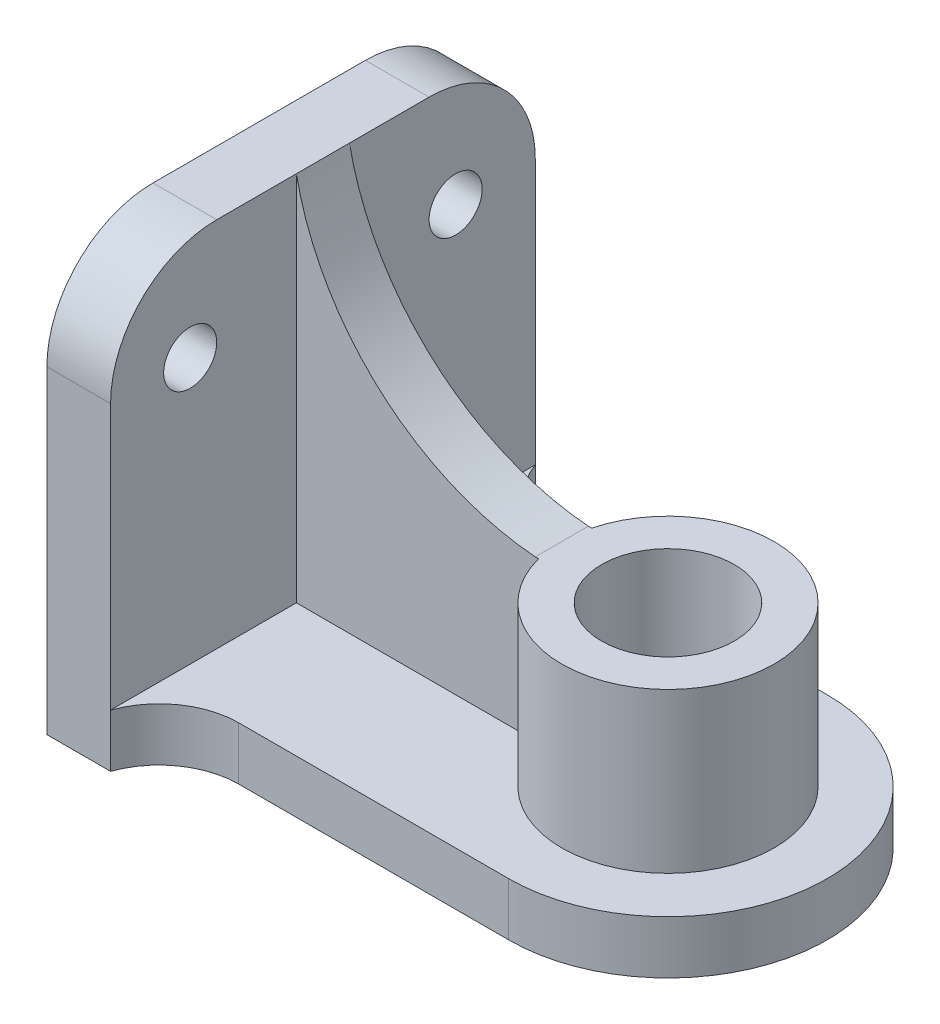
SolidWorks part; units mm, degrees
ref_plane "Front Plane" through (0, 0, 0) normal (0, 0, 1) x (1, 0, 0)
ref_plane "Top Plane" through (0, 0, 0) normal (0, 1, 0) x (1, 0, 0)
ref_plane "Right Plane" through (0, 0, 0) normal (1, 0, 0) x (0, 0, -1)
sketch "Sketch1" plane through (0, 0, 0) normal (0, 1, 0) x (1, 0, 0)
  line L0 (0, 0) -> (0, -80)
  line L1 (0, -80) -> (12, -80)
  line L2 (12, -80) -> (12, 0)
  line L3 (12, 0) -> (0, 0)
  line L4 (77, -1039.1946) -> (77, 48960.8054) construction
  line L5 (-107, -40) -> (107, -40)
  line L6 (77, -70) -> (26.1421, -70)
  line L7 (77, -10) -> (26.1421, -10)
  circle A0 centre (77, -40) radius 20
  circle A1 centre (77, -40) radius 12.5
  arc A2 (77, -70) -> (77, -10) centre (77, -40) ccw
  arc A4 (26.1421, -70) -> (12, -80) centre (26.1421, -85) ccw
  arc A5 (26.1421, -10) -> (12, 0) centre (26.1421, 5) cw
  point P10 (0, -40)
  dimension "D4" = 40
  dimension "D5" = 25
  dimension "D6" = 60
  dimension "D7" = 15
  dimension "D1" = 80
  dimension "D2" = 12
  dimension "D3" = 65
extrude "Boss-Extrude3" add sketch "Sketch1" along normal blind 10 contours L6 L4 A0 L5 L2 A4 | A0 L4 L7 A5 L2 L5 | L4 A0 L5 A2 | L4 A2 L5 A0 region at (39.3253, 0, 23.3734) region at (39.3253, 0, 56.6266) region at (93.1277, 0, 23.8723) region at (93.1277, 0, 56.1277)
extrude "Boss-Extrude4" add sketch "Sketch1<6>" along normal blind 80 contours L0 L5 L2 L3 | L5 L0 L1 L2 region at (6, 0, 20) region at (6, 0, 60)
sketch "Sketch1<6>" plane through (0, 0, 0) normal (0, 1, 0) x (1, 0, 0) same geometry as "Sketch1"
fillet "Fillet1" radius 20 2 edges at (6, 80, 0) (6, 80, 80)
extrude "Boss-Extrude5" add sketch "Sketch1<8>" along normal blind 40 contours L4 A1 L5 A0 | A1 L4 A0 L5 | A0 L4 A1 L5 | L4 A0 L5 A1 region at (66.4713, 0, 29.4713) region at (66.4713, 0, 50.5287) region at (87.5287, 0, 29.4713) region at (87.5287, 0, 50.5287)
sketch "Sketch1<8>" plane through (0, 0, 0) normal (0, 1, 0) x (1, 0, 0) same geometry as "Sketch1"
ref_plane "Plane2" through (12, 0, 0) normal (1, 0, 0) x (0, 0, -1)
sketch "Sketch3" plane through (12, 0, 0) normal (1, 0, 0) x (0, 0, -1)
  line L0 (-45, 80) -> (-45, 10)
  line L1 (-60, 80) -> (-20, 80) construction
  line L2 (-10, 10) -> (-70, 10) construction
  line L3 (-40, 80) -> (-40, 10) construction
  line L4 (-35, 80) -> (-35, 10)
  point P10 (0, 0)
  dimension "D1" = 10
ref_plane "Plane3" through (0, 0, 80) normal (0, 0, 1) x (1, 0, 0)
ref_plane "Plane4" through (57, 0, 0) normal (-1, 0, 0) x (0, 0, 1)
sketch "Sketch6" plane through (57, 0, 0) normal (-1, 0, 0) x (0, 0, 1)
  line L0 (45, 40) -> (45, 10)
  line L1 (45, 80) -> (45, 10) construction
  line L2 (60, 40) -> (20, 40) construction
  line L3 (35, 10) -> (35, 40)
  line L4 (35, 80) -> (35, 10) construction
  line L5 (52.5, 40) -> (27.5, 40) construction
  line L6 (35, 40) -> (45, 40)
  line L7 (45, 10) -> (35, 10)
ref_plane "Plane6" through (0, 0, 45) normal (0, 0, 1) x (1, 0, 0)
sketch "Sketch9" plane through (0, 0, 45) normal (0, 0, 1) x (1, 0, 0)
  line L0 (12, 80) -> (12, 10)
  line L1 (12, 10) -> (57, 10)
  line L2 (57, 10) -> (57, 40)
  arc A0 (12, 80) -> (57, 40) centre (61.0226, 89.8379) ccw
  dimension "D1" = 100
ref_plane "Plane7" through (0, 0, 35) normal (0, 0, 1) x (1, 0, 0)
sketch "Sketch10" plane through (0, 0, 35) normal (0, 0, 1) x (1, 0, 0)
  line L0 (12, 80) -> (12, 10)
  line L1 (12, 10) -> (57, 10)
  line L2 (57, 10) -> (57, 40)
  arc A0 (12, 80) -> (57, 40) centre (61.0226, 89.8379) ccw
  dimension "D1" = 100
ref_plane "Plane8" through (0, 0, 40) normal (0, 0, 1) x (1, 0, 0)
sketch "Sketch11" plane through (0, 0, 40) normal (0, 0, 1) x (1, 0, 0)
  line L0 (12, 80) -> (12, 10)
  line L1 (12, 10) -> (57, 10)
  line L3 (57, 40) -> (57, 10) construction
  line L4 (64.5, 40) -> (64.5, 10)
  line L5 (57, 10) -> (64.5, 10)
  line L6 (57, 40) -> (64.5, 40)
  arc A0 (12, 80) -> (57, 40) centre (61.0226, 89.8379) ccw
  dimension "D1" = 100
extrude "Boss-Extrude11" add sketch "Sketch11" along normal mid plane 10
ref_plane "Plane9" through (12, 0, 0) normal (1, 0, 0) x (0, 0, -1)
sketch "Sketch12" plane through (12, 0, 0) normal (1, 0, 0) x (0, 0, -1)
  line L0 (-60, 80) -> (-45, 80) construction
  line L1 (-80, 60) -> (-80, 10) construction
  line L2 (0, 60) -> (0, 10) construction
  circle A0 centre (-65, 60) radius 5
  circle A1 centre (-15, 60) radius 5
  point P6 (-61.5348, 60)
  point P9 (0, 0)
  dimension "D1" = 10
  dimension "D2" = 20
  dimension "D3" = 15
  dimension "D4" = 15
extrude "Cut-Extrude1" cut sketch "Sketch12" against normal through all
